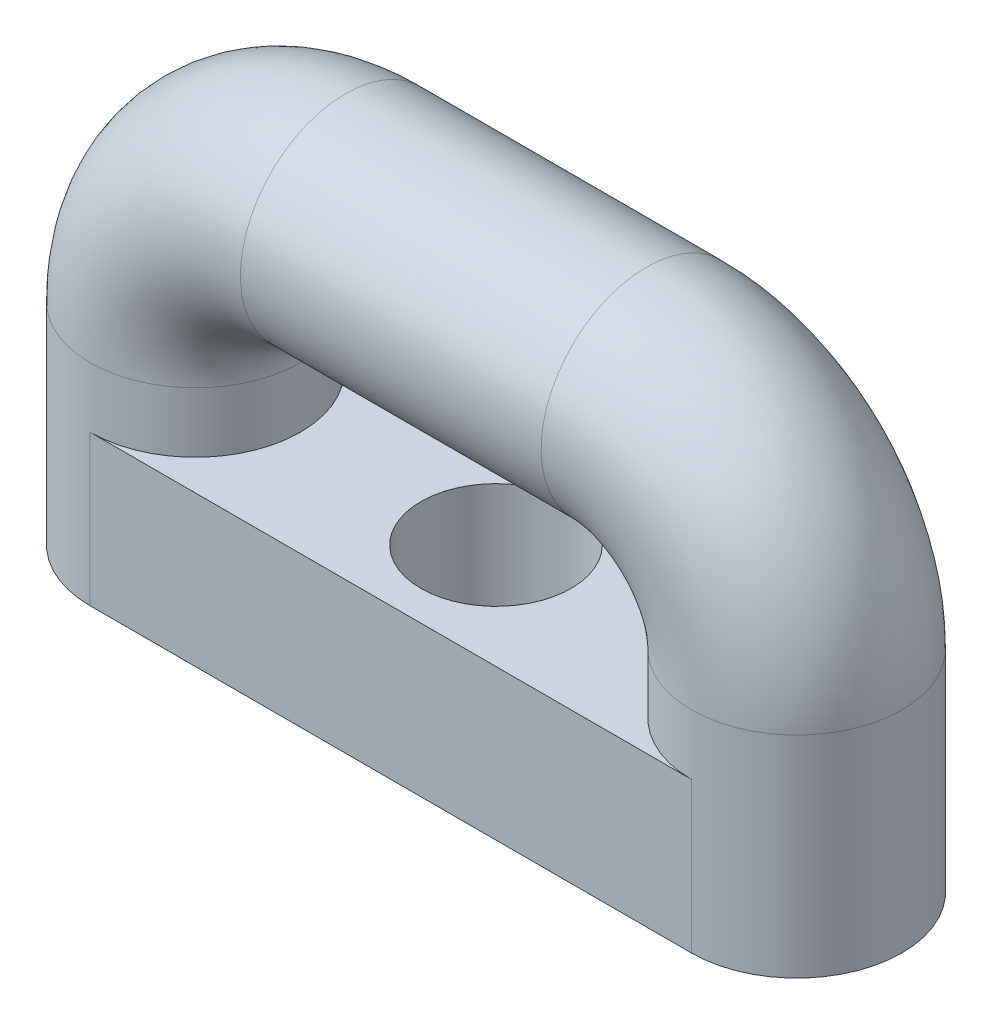
SolidWorks part; units mm, degrees
material "ABS"
ref_plane "Front Plane" through (0, 0, 0) normal (0, 0, 1) x (1, 0, 0)
ref_plane "Top Plane" through (0, 0, 0) normal (0, 1, 0) x (1, 0, 0)
ref_plane "Right Plane" through (0, 0, 0) normal (1, 0, 0) x (0, 0, -1)
sketch "Sketch1" plane through (0, 0, 0) normal (0, 1, 0) x (1, 0, 0)
  line L1 (-12.7, -4.445) -> (12.7, -4.445)
  line L3 (-12.7, 4.445) -> (12.7, 4.445)
  line L5 (-12.7, -4.445) -> (12.7, 4.445) construction
  line L6 (-12.7, 4.445) -> (12.7, -4.445) construction
  arc A0 (-12.7, 4.445) -> (-12.7, -4.445) centre (-12.7, 0) ccw
  arc A1 (12.7, -4.445) -> (12.7, 4.445) centre (12.7, 0) ccw
  point P0 (0, 0)
  dimension "D2" = 8.89
  dimension "D1" = 25.4
extrude "Boss-Extrude1" add sketch "Sketch1" along normal blind 6.35 contours A0 L1 A1 L3
sketch "Sketch2" plane through (0, 6.35, 0) normal (0, 1, 0) x (1, 0, 0)
  circle A0 centre (-12.7, 0) radius 4.445
  circle A1 centre (12.7, 0) radius 4.445
  point P7 (0, 0)
sketch "Sketch3" plane through (0, 0, 0) normal (0, 0, 1) x (1, 0, 0)
  line L0 (-12.7, 6.35) -> (-12.7, 8.89)
  line L1 (12.7, 6.35) -> (12.7, 8.89)
  line L2 (-6.35, 15.24) -> (6.35, 15.24)
  line L3 (-17.145, 0) -> (-12.7, 0) construction
  arc A0 (-12.7, 8.89) -> (-6.35, 15.24) centre (-6.35, 8.89) cw
  arc A1 (12.7, 8.89) -> (6.35, 15.24) centre (6.35, 8.89) ccw
  point P10 (-12.7, 15.24)
  dimension "D2" = 6.35
  dimension "D1" = 15.24
sweep "Sweep1" add path "Sketch3" circular profile diameter 8.89 parameters "D3"=8.89
sketch "Sketch11" plane through (0, 6.35, 0) normal (0, 1, 0) x (1, 0, 0)
  circle A0 centre (0, 0) radius 3.175
  dimension "D1" = 6.35
extrude "Cut-Extrude1" cut sketch "Sketch11" against normal through all
